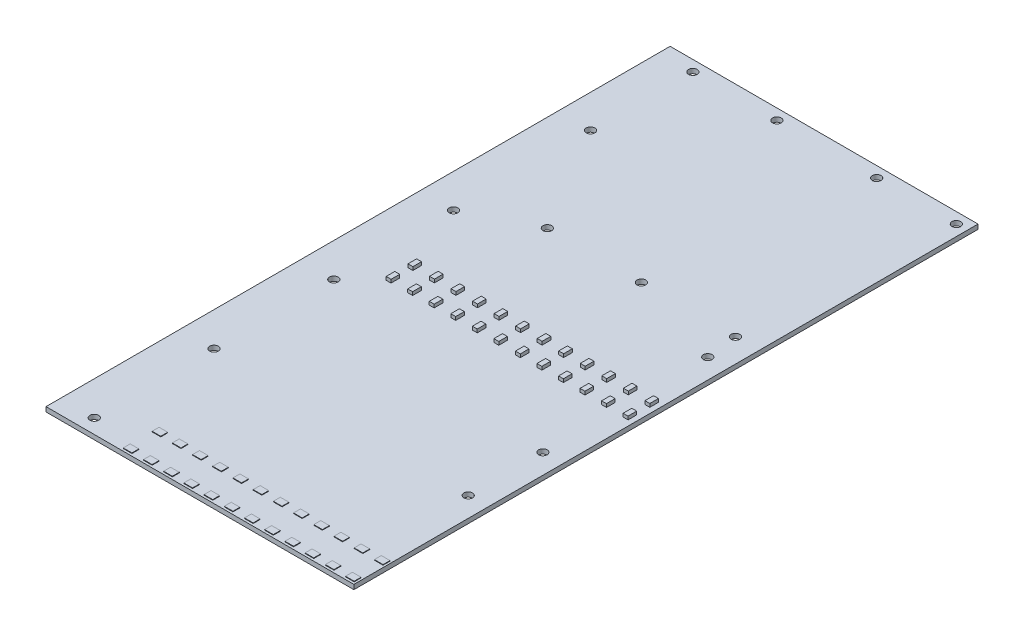
SolidWorks part; units mm, degrees
ref_plane "Front Plane" through (0, 0, 0) normal (0, 0, 1) x (1, 0, 0)
ref_plane "Top Plane" through (0, 0, 0) normal (0, 1, 0) x (1, 0, 0)
ref_plane "Right Plane" through (0, 0, 0) normal (1, 0, 0) x (0, 0, -1)
sketch "Sketch1" plane through (0, 0, 0) normal (0, 1, 0) x (1, 0, 0)
  line L1 (-53.335, 108.115) -> (53.335, 108.115)
  line L2 (-53.335, 108.115) -> (-53.335, -108.115)
  line L3 (-53.335, -108.115) -> (53.335, -108.115)
  line L4 (53.335, 108.115) -> (53.335, -108.115)
  line L5 (-53.335, 108.115) -> (53.335, -108.115) construction
  line L6 (-53.335, -108.115) -> (53.335, 108.115) construction
  point P0 (0, 0)
  dimension "D1" = 106.67
  dimension "D2" = 216.23
extrude "Boss-Extrude1" add sketch "Sketch1" along normal blind 1.6
ref_plane "Plane1" through (0, 0.8, 0) normal (0, -1, 0) x (-1, 0, 0)
sketch "Sketch4"
  dimension "D1" = 53.04
  dimension "D2" = 81.4
sketch_block_instance "motorBaseHoles-1"
sketch_block "Block1" parameters "D3"=3, "D7"=4.8524, "D1"=81.2, "D2"=7, "D4"=7, "D5"=7, "D6"=4.4351
sketch "Sketch6" plane through (0, 0, 0) normal (0, -1, 0) x (1, 0, 0)
  line L0 (12.635, 97.5334) -> (12.635, 107.6142) construction
  line L1 (-53.335, 108.115) -> (53.335, 108.115) construction
  line L2 (-25.865, 107.115) -> (-25.865, 97.1142) construction
  line L3 (-27.215, 107.115) -> (-24.515, 107.115) construction
  line L4 (-27.215, 107.115) -> (-27.215, 95.115) construction
  line L5 (-27.215, 95.115) -> (-24.515, 95.115) construction
  line L6 (-24.515, 107.115) -> (-24.515, 95.115) construction
  line L7 (-25.865, 104.915) -> (-25.865, 107.115) construction
  line L8 (-27.365, 107.315) -> (-24.365, 107.315)
  line L9 (-27.365, 107.315) -> (-27.365, 104.915)
  line L10 (-27.365, 104.915) -> (-24.365, 104.915)
  line L11 (-24.365, 107.315) -> (-24.365, 104.915)
  line L12 (-27.215, 101.115) -> (-24.515, 101.115) construction
  line L13 (-24.365, 94.915) -> (-24.365, 97.315)
  line L14 (-27.365, 97.315) -> (-24.365, 97.315)
  line L15 (-27.365, 94.915) -> (-27.365, 97.315)
  line L16 (-27.365, 94.915) -> (-24.365, 94.915)
  line L17 (-20.365, 107.315) -> (-17.365, 107.315)
  line L18 (-20.365, 107.315) -> (-20.365, 104.915)
  line L19 (-20.365, 104.915) -> (-17.365, 104.915)
  line L20 (-17.365, 107.315) -> (-17.365, 104.915)
  line L21 (-17.365, 94.915) -> (-17.365, 97.315)
  line L22 (-20.365, 97.315) -> (-17.365, 97.315)
  line L23 (-20.365, 94.915) -> (-20.365, 97.315)
  line L24 (-20.365, 94.915) -> (-17.365, 94.915)
  line L25 (-20.215, 107.115) -> (-17.515, 107.115) construction
  line L26 (-20.215, 107.115) -> (-20.215, 95.115) construction
  line L27 (-20.215, 95.115) -> (-17.515, 95.115) construction
  line L28 (-17.515, 107.115) -> (-17.515, 95.115) construction
  line L29 (-18.865, 104.915) -> (-18.865, 107.115) construction
  line L30 (-20.215, 101.115) -> (-17.515, 101.115) construction
  line L31 (-13.365, 107.315) -> (-10.365, 107.315)
  line L32 (-13.365, 107.315) -> (-13.365, 104.915)
  line L33 (-13.365, 104.915) -> (-10.365, 104.915)
  line L34 (-10.365, 107.315) -> (-10.365, 104.915)
  line L35 (-10.365, 94.915) -> (-10.365, 97.315)
  line L36 (-13.365, 97.315) -> (-10.365, 97.315)
  line L37 (-13.365, 94.915) -> (-13.365, 97.315)
  line L38 (-13.365, 94.915) -> (-10.365, 94.915)
  line L39 (-13.215, 107.115) -> (-10.515, 107.115) construction
  line L40 (-13.215, 107.115) -> (-13.215, 95.115) construction
  line L41 (-13.215, 95.115) -> (-10.515, 95.115) construction
  line L42 (-10.515, 107.115) -> (-10.515, 95.115) construction
  line L43 (-11.865, 104.915) -> (-11.865, 107.115) construction
  line L44 (-13.215, 101.115) -> (-10.515, 101.115) construction
  line L45 (-6.365, 107.315) -> (-3.365, 107.315)
  line L46 (-6.365, 107.315) -> (-6.365, 104.915)
  line L47 (-6.365, 104.915) -> (-3.365, 104.915)
  line L48 (-3.365, 107.315) -> (-3.365, 104.915)
  line L49 (-3.365, 94.915) -> (-3.365, 97.315)
  line L50 (-6.365, 97.315) -> (-3.365, 97.315)
  line L51 (-6.365, 94.915) -> (-6.365, 97.315)
  line L52 (-6.365, 94.915) -> (-3.365, 94.915)
  line L53 (-6.215, 107.115) -> (-3.515, 107.115) construction
  line L54 (-6.215, 107.115) -> (-6.215, 95.115) construction
  line L55 (-6.215, 95.115) -> (-3.515, 95.115) construction
  line L56 (-3.515, 107.115) -> (-3.515, 95.115) construction
  line L57 (-4.865, 104.915) -> (-4.865, 107.115) construction
  line L58 (-6.215, 101.115) -> (-3.515, 101.115) construction
  line L59 (0.635, 107.315) -> (3.635, 107.315)
  line L60 (0.635, 107.315) -> (0.635, 104.915)
  line L61 (0.635, 104.915) -> (3.635, 104.915)
  line L62 (3.635, 107.315) -> (3.635, 104.915)
  line L63 (3.635, 94.915) -> (3.635, 97.315)
  line L64 (0.635, 97.315) -> (3.635, 97.315)
  line L65 (0.635, 94.915) -> (0.635, 97.315)
  line L66 (0.635, 94.915) -> (3.635, 94.915)
  line L67 (0.785, 107.115) -> (3.485, 107.115) construction
  line L68 (0.785, 107.115) -> (0.785, 95.115) construction
  line L69 (0.785, 95.115) -> (3.485, 95.115) construction
  line L70 (3.485, 107.115) -> (3.485, 95.115) construction
  line L71 (2.135, 104.915) -> (2.135, 107.115) construction
  line L72 (0.785, 101.115) -> (3.485, 101.115) construction
  line L73 (7.635, 107.315) -> (10.635, 107.315)
  line L74 (7.635, 107.315) -> (7.635, 104.915)
  line L75 (7.635, 104.915) -> (10.635, 104.915)
  line L76 (10.635, 107.315) -> (10.635, 104.915)
  line L77 (10.635, 94.915) -> (10.635, 97.315)
  line L78 (7.635, 97.315) -> (10.635, 97.315)
  line L79 (7.635, 94.915) -> (7.635, 97.315)
  line L80 (7.635, 94.915) -> (10.635, 94.915)
  line L81 (7.785, 107.115) -> (10.485, 107.115) construction
  line L82 (7.785, 107.115) -> (7.785, 95.115) construction
  line L83 (7.785, 95.115) -> (10.485, 95.115) construction
  line L84 (10.485, 107.115) -> (10.485, 95.115) construction
  line L85 (9.135, 104.915) -> (9.135, 107.115) construction
  line L86 (7.785, 101.115) -> (10.485, 101.115) construction
  line L87 (14.635, 107.315) -> (17.635, 107.315)
  line L88 (14.635, 107.315) -> (14.635, 104.915)
  line L89 (14.635, 104.915) -> (17.635, 104.915)
  line L90 (17.635, 107.315) -> (17.635, 104.915)
  line L91 (17.635, 94.915) -> (17.635, 97.315)
  line L92 (14.635, 97.315) -> (17.635, 97.315)
  line L93 (14.635, 94.915) -> (14.635, 97.315)
  line L94 (14.635, 94.915) -> (17.635, 94.915)
  line L95 (14.785, 107.115) -> (17.485, 107.115) construction
  line L96 (14.785, 107.115) -> (14.785, 95.115) construction
  line L97 (14.785, 95.115) -> (17.485, 95.115) construction
  line L98 (17.485, 107.115) -> (17.485, 95.115) construction
  line L99 (16.135, 104.915) -> (16.135, 107.115) construction
  line L100 (14.785, 101.115) -> (17.485, 101.115) construction
  line L101 (21.635, 107.315) -> (24.635, 107.315)
  line L102 (21.635, 107.315) -> (21.635, 104.915)
  line L103 (21.635, 104.915) -> (24.635, 104.915)
  line L104 (24.635, 107.315) -> (24.635, 104.915)
  line L105 (24.635, 94.915) -> (24.635, 97.315)
  line L106 (21.635, 97.315) -> (24.635, 97.315)
  line L107 (21.635, 94.915) -> (21.635, 97.315)
  line L108 (21.635, 94.915) -> (24.635, 94.915)
  line L109 (21.785, 107.115) -> (24.485, 107.115) construction
  line L110 (21.785, 107.115) -> (21.785, 95.115) construction
  line L111 (21.785, 95.115) -> (24.485, 95.115) construction
  line L112 (24.485, 107.115) -> (24.485, 95.115) construction
  line L113 (23.135, 104.915) -> (23.135, 107.115) construction
  line L114 (21.785, 101.115) -> (24.485, 101.115) construction
  line L115 (28.635, 107.315) -> (31.635, 107.315)
  line L116 (28.635, 107.315) -> (28.635, 104.915)
  line L117 (28.635, 104.915) -> (31.635, 104.915)
  line L118 (31.635, 107.315) -> (31.635, 104.915)
  line L119 (31.635, 94.915) -> (31.635, 97.315)
  line L120 (28.635, 97.315) -> (31.635, 97.315)
  line L121 (28.635, 94.915) -> (28.635, 97.315)
  line L122 (28.635, 94.915) -> (31.635, 94.915)
  line L123 (28.785, 107.115) -> (31.485, 107.115) construction
  line L124 (28.785, 107.115) -> (28.785, 95.115) construction
  line L125 (28.785, 95.115) -> (31.485, 95.115) construction
  line L126 (31.485, 107.115) -> (31.485, 95.115) construction
  line L127 (30.135, 104.915) -> (30.135, 107.115) construction
  line L128 (28.785, 101.115) -> (31.485, 101.115) construction
  line L129 (35.635, 107.315) -> (38.635, 107.315)
  line L130 (35.635, 107.315) -> (35.635, 104.915)
  line L131 (35.635, 104.915) -> (38.635, 104.915)
  line L132 (38.635, 107.315) -> (38.635, 104.915)
  line L133 (38.635, 94.915) -> (38.635, 97.315)
  line L134 (35.635, 97.315) -> (38.635, 97.315)
  line L135 (35.635, 94.915) -> (35.635, 97.315)
  line L136 (35.635, 94.915) -> (38.635, 94.915)
  line L137 (35.785, 107.115) -> (38.485, 107.115) construction
  line L138 (35.785, 107.115) -> (35.785, 95.115) construction
  line L139 (35.785, 95.115) -> (38.485, 95.115) construction
  line L140 (38.485, 107.115) -> (38.485, 95.115) construction
  line L141 (37.135, 104.915) -> (37.135, 107.115) construction
  line L142 (35.785, 101.115) -> (38.485, 101.115) construction
  line L143 (42.635, 107.315) -> (45.635, 107.315)
  line L144 (42.635, 107.315) -> (42.635, 104.915)
  line L145 (42.635, 104.915) -> (45.635, 104.915)
  line L146 (45.635, 107.315) -> (45.635, 104.915)
  line L147 (45.635, 94.915) -> (45.635, 97.315)
  line L148 (42.635, 97.315) -> (45.635, 97.315)
  line L149 (42.635, 94.915) -> (42.635, 97.315)
  line L150 (42.635, 94.915) -> (45.635, 94.915)
  line L151 (42.785, 107.115) -> (45.485, 107.115) construction
  line L152 (42.785, 107.115) -> (42.785, 95.115) construction
  line L153 (42.785, 95.115) -> (45.485, 95.115) construction
  line L154 (45.485, 107.115) -> (45.485, 95.115) construction
  line L155 (44.135, 104.915) -> (44.135, 107.115) construction
  line L156 (42.785, 101.115) -> (45.485, 101.115) construction
  line L157 (49.635, 107.315) -> (52.635, 107.315)
  line L158 (49.635, 107.315) -> (49.635, 104.915)
  line L159 (49.635, 104.915) -> (52.635, 104.915)
  line L160 (52.635, 107.315) -> (52.635, 104.915)
  line L161 (52.635, 94.915) -> (52.635, 97.315)
  line L162 (49.635, 97.315) -> (52.635, 97.315)
  line L163 (49.635, 94.915) -> (49.635, 97.315)
  line L164 (49.635, 94.915) -> (52.635, 94.915)
  line L165 (49.785, 107.115) -> (52.485, 107.115) construction
  line L166 (49.785, 107.115) -> (49.785, 95.115) construction
  line L167 (49.785, 95.115) -> (52.485, 95.115) construction
  line L168 (52.485, 107.115) -> (52.485, 95.115) construction
  line L169 (51.135, 104.915) -> (51.135, 107.115) construction
  line L170 (49.785, 101.115) -> (52.485, 101.115) construction
  line L171 (51.135, 107.115) -> (51.135, 97.1142) construction
  line L172 (53.335, 0) -> (-28.065, 0) construction
  line L173 (53.335, 0) -> (-28.065, 0) construction
  line L174 (12.635, 0) -> (12.635, 97.5334) construction
  line B0 (-21.365, 120.6142) -> (-16.365, 120.6142) construction
  line B1 (-28.865, 121.1142) -> (-22.865, 121.1142) construction
  line B2 (-28.865, 121.1142) -> (-28.865, 115.1142) construction
  line B3 (-28.865, 115.1142) -> (-22.865, 115.1142) construction
  line B4 (-22.865, 121.1142) -> (-22.865, 115.1142) construction
  line B5 (-28.865, 121.1142) -> (-22.865, 115.1142) construction
  line B6 (-28.865, 115.1142) -> (-22.865, 121.1142) construction
  line B7 (-28.365, 120.6142) -> (-23.365, 120.6142) construction
  line B8 (-28.365, 120.6142) -> (-28.365, 115.6142) construction
  line B9 (-28.365, 115.6142) -> (-23.365, 115.6142) construction
  line B10 (-23.365, 120.6142) -> (-23.365, 115.6142) construction
  line B11 (-28.365, 120.6142) -> (-23.365, 115.6142) construction
  line B12 (-28.365, 115.6142) -> (-23.365, 120.6142) construction
  line B13 (-21.365, 120.6142) -> (-21.365, 115.6142) construction
  line B14 (-21.365, 115.6142) -> (-16.365, 115.6142) construction
  line B15 (-16.365, 120.6142) -> (-16.365, 115.6142) construction
  line B16 (-21.865, 121.1142) -> (-15.865, 121.1142) construction
  line B17 (-21.865, 121.1142) -> (-21.865, 115.1142) construction
  line B18 (-21.865, 115.1142) -> (-15.865, 115.1142) construction
  line B19 (-15.865, 121.1142) -> (-15.865, 115.1142) construction
  line B20 (-21.865, 121.1142) -> (-15.865, 115.1142) construction
  line B21 (-21.865, 115.1142) -> (-15.865, 121.1142) construction
  line B22 (-21.365, 120.6142) -> (-16.365, 115.6142) construction
  line B23 (-21.365, 115.6142) -> (-16.365, 120.6142) construction
  line B24 (-14.365, 120.6142) -> (-9.365, 120.6142) construction
  line B25 (-14.365, 120.6142) -> (-14.365, 115.6142) construction
  line B26 (-14.365, 115.6142) -> (-9.365, 115.6142) construction
  line B27 (-9.365, 120.6142) -> (-9.365, 115.6142) construction
  line B28 (-14.865, 121.1142) -> (-8.865, 121.1142) construction
  line B29 (-14.865, 121.1142) -> (-14.865, 115.1142) construction
  line B30 (-14.865, 115.1142) -> (-8.865, 115.1142) construction
  line B31 (-8.865, 121.1142) -> (-8.865, 115.1142) construction
  line B32 (-14.865, 121.1142) -> (-8.865, 115.1142) construction
  line B33 (-14.865, 115.1142) -> (-8.865, 121.1142) construction
  line B34 (-14.365, 120.6142) -> (-9.365, 115.6142) construction
  line B35 (-14.365, 115.6142) -> (-9.365, 120.6142) construction
  line B36 (-7.365, 120.6142) -> (-2.365, 120.6142) construction
  line B37 (-7.365, 120.6142) -> (-7.365, 115.6142) construction
  line B38 (-7.365, 115.6142) -> (-2.365, 115.6142) construction
  line B39 (-2.365, 120.6142) -> (-2.365, 115.6142) construction
  line B40 (-7.865, 121.1142) -> (-1.865, 121.1142) construction
  line B41 (-7.865, 121.1142) -> (-7.865, 115.1142) construction
  line B42 (-7.865, 115.1142) -> (-1.865, 115.1142) construction
  line B43 (-1.865, 121.1142) -> (-1.865, 115.1142) construction
  line B44 (-7.865, 121.1142) -> (-1.865, 115.1142) construction
  line B45 (-7.865, 115.1142) -> (-1.865, 121.1142) construction
  line B46 (-7.365, 120.6142) -> (-2.365, 115.6142) construction
  line B47 (-7.365, 115.6142) -> (-2.365, 120.6142) construction
  line B48 (-0.365, 120.6142) -> (4.635, 120.6142) construction
  line B49 (-0.365, 120.6142) -> (-0.365, 115.6142) construction
  line B50 (-0.365, 115.6142) -> (4.635, 115.6142) construction
  line B51 (4.635, 120.6142) -> (4.635, 115.6142) construction
  line B52 (-0.865, 121.1142) -> (5.135, 121.1142) construction
  line B53 (-0.865, 121.1142) -> (-0.865, 115.1142) construction
  line B54 (-0.865, 115.1142) -> (5.135, 115.1142) construction
  line B55 (5.135, 121.1142) -> (5.135, 115.1142) construction
  line B56 (-0.865, 121.1142) -> (5.135, 115.1142) construction
  line B57 (-0.865, 115.1142) -> (5.135, 121.1142) construction
  line B58 (-0.365, 120.6142) -> (4.635, 115.6142) construction
  line B59 (-0.365, 115.6142) -> (4.635, 120.6142) construction
  line B60 (6.635, 120.6142) -> (11.635, 120.6142) construction
  line B61 (6.635, 120.6142) -> (6.635, 115.6142) construction
  line B62 (6.635, 115.6142) -> (11.635, 115.6142) construction
  line B63 (11.635, 120.6142) -> (11.635, 115.6142) construction
  line B64 (6.135, 121.1142) -> (12.135, 121.1142) construction
  line B65 (6.135, 121.1142) -> (6.135, 115.1142) construction
  line B66 (6.135, 115.1142) -> (12.135, 115.1142) construction
  line B67 (12.135, 121.1142) -> (12.135, 115.1142) construction
  line B68 (6.135, 121.1142) -> (12.135, 115.1142) construction
  line B69 (6.135, 115.1142) -> (12.135, 121.1142) construction
  line B70 (6.635, 120.6142) -> (11.635, 115.6142) construction
  line B71 (6.635, 115.6142) -> (11.635, 120.6142) construction
  line B72 (13.635, 120.6142) -> (18.635, 120.6142) construction
  line B73 (13.635, 120.6142) -> (13.635, 115.6142) construction
  line B74 (13.635, 115.6142) -> (18.635, 115.6142) construction
  line B75 (18.635, 120.6142) -> (18.635, 115.6142) construction
  line B76 (13.135, 121.1142) -> (19.135, 121.1142) construction
  line B77 (13.135, 121.1142) -> (13.135, 115.1142) construction
  line B78 (13.135, 115.1142) -> (19.135, 115.1142) construction
  line B79 (19.135, 121.1142) -> (19.135, 115.1142) construction
  line B80 (13.135, 121.1142) -> (19.135, 115.1142) construction
  line B81 (13.135, 115.1142) -> (19.135, 121.1142) construction
  line B82 (13.635, 120.6142) -> (18.635, 115.6142) construction
  line B83 (13.635, 115.6142) -> (18.635, 120.6142) construction
  line B84 (20.635, 120.6142) -> (25.635, 120.6142) construction
  line B85 (20.635, 120.6142) -> (20.635, 115.6142) construction
  line B86 (20.635, 115.6142) -> (25.635, 115.6142) construction
  line B87 (25.635, 120.6142) -> (25.635, 115.6142) construction
  line B88 (20.135, 121.1142) -> (26.135, 121.1142) construction
  line B89 (20.135, 121.1142) -> (20.135, 115.1142) construction
  line B90 (20.135, 115.1142) -> (26.135, 115.1142) construction
  line B91 (26.135, 121.1142) -> (26.135, 115.1142) construction
  line B92 (20.135, 121.1142) -> (26.135, 115.1142) construction
  line B93 (20.135, 115.1142) -> (26.135, 121.1142) construction
  line B94 (20.635, 120.6142) -> (25.635, 115.6142) construction
  line B95 (20.635, 115.6142) -> (25.635, 120.6142) construction
  line B96 (27.635, 120.6142) -> (32.635, 120.6142) construction
  line B97 (27.635, 120.6142) -> (27.635, 115.6142) construction
  line B98 (27.635, 115.6142) -> (32.635, 115.6142) construction
  line B99 (32.635, 120.6142) -> (32.635, 115.6142) construction
  line B100 (27.135, 121.1142) -> (33.135, 121.1142) construction
  line B101 (27.135, 121.1142) -> (27.135, 115.1142) construction
  line B102 (27.135, 115.1142) -> (33.135, 115.1142) construction
  line B103 (33.135, 121.1142) -> (33.135, 115.1142) construction
  line B104 (27.135, 121.1142) -> (33.135, 115.1142) construction
  line B105 (27.135, 115.1142) -> (33.135, 121.1142) construction
  line B106 (27.635, 120.6142) -> (32.635, 115.6142) construction
  line B107 (27.635, 115.6142) -> (32.635, 120.6142) construction
  line B108 (34.635, 120.6142) -> (39.635, 120.6142) construction
  line B109 (34.635, 120.6142) -> (34.635, 115.6142) construction
  line B110 (34.635, 115.6142) -> (39.635, 115.6142) construction
  line B111 (39.635, 120.6142) -> (39.635, 115.6142) construction
  line B112 (34.135, 121.1142) -> (40.135, 121.1142) construction
  line B113 (34.135, 121.1142) -> (34.135, 115.1142) construction
  line B114 (34.135, 115.1142) -> (40.135, 115.1142) construction
  line B115 (40.135, 121.1142) -> (40.135, 115.1142) construction
  line B116 (34.135, 121.1142) -> (40.135, 115.1142) construction
  line B117 (34.135, 115.1142) -> (40.135, 121.1142) construction
  line B118 (34.635, 120.6142) -> (39.635, 115.6142) construction
  line B119 (34.635, 115.6142) -> (39.635, 120.6142) construction
  line B120 (41.635, 120.6142) -> (46.635, 120.6142) construction
  line B121 (41.635, 120.6142) -> (41.635, 115.6142) construction
  line B122 (41.635, 115.6142) -> (46.635, 115.6142) construction
  line B123 (46.635, 120.6142) -> (46.635, 115.6142) construction
  line B124 (41.135, 121.1142) -> (47.135, 121.1142) construction
  line B125 (41.135, 121.1142) -> (41.135, 115.1142) construction
  line B126 (41.135, 115.1142) -> (47.135, 115.1142) construction
  line B127 (47.135, 121.1142) -> (47.135, 115.1142) construction
  line B128 (41.135, 121.1142) -> (47.135, 115.1142) construction
  line B129 (41.135, 115.1142) -> (47.135, 121.1142) construction
  line B130 (41.635, 120.6142) -> (46.635, 115.6142) construction
  line B131 (41.635, 115.6142) -> (46.635, 120.6142) construction
  line B132 (48.635, 120.6142) -> (53.635, 120.6142) construction
  line B133 (48.635, 120.6142) -> (48.635, 115.6142) construction
  line B134 (48.635, 115.6142) -> (53.635, 115.6142) construction
  line B135 (53.635, 120.6142) -> (53.635, 115.6142) construction
  line B136 (48.135, 121.1142) -> (54.135, 121.1142) construction
  line B137 (48.135, 121.1142) -> (48.135, 115.1142) construction
  line B138 (48.135, 115.1142) -> (54.135, 115.1142) construction
  line B139 (54.135, 121.1142) -> (54.135, 115.1142) construction
  line B140 (48.135, 121.1142) -> (54.135, 115.1142) construction
  line B141 (48.135, 115.1142) -> (54.135, 121.1142) construction
  line B142 (48.635, 120.6142) -> (53.635, 115.6142) construction
  line B143 (48.635, 115.6142) -> (53.635, 120.6142) construction
  line B144 (-21.365, 113.6142) -> (-16.365, 113.6142) construction
  line B145 (-28.365, 113.6142) -> (-23.365, 113.6142) construction
  line B146 (-28.365, 113.6142) -> (-28.365, 108.6142) construction
  line B147 (-28.365, 108.6142) -> (-23.365, 108.6142) construction
  line B148 (-23.365, 113.6142) -> (-23.365, 108.6142) construction
  line B149 (-21.365, 113.6142) -> (-21.365, 108.6142) construction
  line B150 (-21.365, 108.6142) -> (-16.365, 108.6142) construction
  line B151 (-16.365, 113.6142) -> (-16.365, 108.6142) construction
  line B152 (-14.365, 113.6142) -> (-9.365, 113.6142) construction
  line B153 (-14.365, 113.6142) -> (-14.365, 108.6142) construction
  line B154 (-14.365, 108.6142) -> (-9.365, 108.6142) construction
  line B155 (-9.365, 113.6142) -> (-9.365, 108.6142) construction
  line B156 (-7.365, 113.6142) -> (-2.365, 113.6142) construction
  line B157 (-7.365, 113.6142) -> (-7.365, 108.6142) construction
  line B158 (-7.365, 108.6142) -> (-2.365, 108.6142) construction
  line B159 (-2.365, 113.6142) -> (-2.365, 108.6142) construction
  line B160 (-0.365, 113.6142) -> (4.635, 113.6142) construction
  line B161 (-0.365, 113.6142) -> (-0.365, 108.6142) construction
  line B162 (-0.365, 108.6142) -> (4.635, 108.6142) construction
  line B163 (4.635, 113.6142) -> (4.635, 108.6142) construction
  line B164 (6.635, 113.6142) -> (11.635, 113.6142) construction
  line B165 (6.635, 113.6142) -> (6.635, 108.6142) construction
  line B166 (6.635, 108.6142) -> (11.635, 108.6142) construction
  line B167 (11.635, 113.6142) -> (11.635, 108.6142) construction
  line B168 (13.635, 113.6142) -> (18.635, 113.6142) construction
  line B169 (13.635, 113.6142) -> (13.635, 108.6142) construction
  line B170 (13.635, 108.6142) -> (18.635, 108.6142) construction
  line B171 (18.635, 113.6142) -> (18.635, 108.6142) construction
  line B172 (20.635, 113.6142) -> (25.635, 113.6142) construction
  line B173 (20.635, 113.6142) -> (20.635, 108.6142) construction
  line B174 (20.635, 108.6142) -> (25.635, 108.6142) construction
  line B175 (25.635, 113.6142) -> (25.635, 108.6142) construction
  line B176 (27.635, 113.6142) -> (32.635, 113.6142) construction
  line B177 (27.635, 113.6142) -> (27.635, 108.6142) construction
  line B178 (27.635, 108.6142) -> (32.635, 108.6142) construction
  line B179 (32.635, 113.6142) -> (32.635, 108.6142) construction
  line B180 (34.635, 113.6142) -> (39.635, 113.6142) construction
  line B181 (34.635, 113.6142) -> (34.635, 108.6142) construction
  line B182 (34.635, 108.6142) -> (39.635, 108.6142) construction
  line B183 (39.635, 113.6142) -> (39.635, 108.6142) construction
  line B184 (41.635, 113.6142) -> (46.635, 113.6142) construction
  line B185 (41.635, 113.6142) -> (41.635, 108.6142) construction
  line B186 (41.635, 108.6142) -> (46.635, 108.6142) construction
  line B187 (46.635, 113.6142) -> (46.635, 108.6142) construction
  line B188 (48.635, 113.6142) -> (53.635, 113.6142) construction
  line B189 (48.635, 113.6142) -> (48.635, 108.6142) construction
  line B190 (48.635, 108.6142) -> (53.635, 108.6142) construction
  line B191 (53.635, 113.6142) -> (53.635, 108.6142) construction
  line B192 (-28.865, 114.1142) -> (-22.865, 114.1142) construction
  line B193 (-28.865, 114.1142) -> (-28.865, 108.1142) construction
  line B194 (-28.865, 108.1142) -> (-22.865, 108.1142) construction
  line B195 (-22.865, 114.1142) -> (-22.865, 108.1142) construction
  line B196 (-28.865, 114.1142) -> (-22.865, 108.1142) construction
  line B197 (-28.865, 108.1142) -> (-22.865, 114.1142) construction
  line B198 (-28.365, 113.6142) -> (-23.365, 108.6142) construction
  line B199 (-28.365, 108.6142) -> (-23.365, 113.6142) construction
  line B200 (-21.865, 114.1142) -> (-15.865, 114.1142) construction
  line B201 (-21.865, 114.1142) -> (-21.865, 108.1142) construction
  line B202 (-21.865, 108.1142) -> (-15.865, 108.1142) construction
  line B203 (-15.865, 114.1142) -> (-15.865, 108.1142) construction
  line B204 (-21.865, 114.1142) -> (-15.865, 108.1142) construction
  line B205 (-21.865, 108.1142) -> (-15.865, 114.1142) construction
  line B206 (-21.365, 113.6142) -> (-16.365, 108.6142) construction
  line B207 (-21.365, 108.6142) -> (-16.365, 113.6142) construction
  line B208 (-14.865, 114.1142) -> (-8.865, 114.1142) construction
  line B209 (-14.865, 114.1142) -> (-14.865, 108.1142) construction
  line B210 (-14.865, 108.1142) -> (-8.865, 108.1142) construction
  line B211 (-8.865, 114.1142) -> (-8.865, 108.1142) construction
  line B212 (-14.865, 114.1142) -> (-8.865, 108.1142) construction
  line B213 (-14.865, 108.1142) -> (-8.865, 114.1142) construction
  line B214 (-14.365, 113.6142) -> (-9.365, 108.6142) construction
  line B215 (-14.365, 108.6142) -> (-9.365, 113.6142) construction
  line B216 (-7.865, 114.1142) -> (-1.865, 114.1142) construction
  line B217 (-7.865, 114.1142) -> (-7.865, 108.1142) construction
  line B218 (-7.865, 108.1142) -> (-1.865, 108.1142) construction
  line B219 (-1.865, 114.1142) -> (-1.865, 108.1142) construction
  line B220 (-7.865, 114.1142) -> (-1.865, 108.1142) construction
  line B221 (-7.865, 108.1142) -> (-1.865, 114.1142) construction
  line B222 (-7.365, 113.6142) -> (-2.365, 108.6142) construction
  line B223 (-7.365, 108.6142) -> (-2.365, 113.6142) construction
  line B224 (-0.865, 114.1142) -> (5.135, 114.1142) construction
  line B225 (-0.865, 114.1142) -> (-0.865, 108.1142) construction
  line B226 (-0.865, 108.1142) -> (5.135, 108.1142) construction
  line B227 (5.135, 114.1142) -> (5.135, 108.1142) construction
  line B228 (-0.865, 114.1142) -> (5.135, 108.1142) construction
  line B229 (-0.865, 108.1142) -> (5.135, 114.1142) construction
  line B230 (-0.365, 113.6142) -> (4.635, 108.6142) construction
  line B231 (-0.365, 108.6142) -> (4.635, 113.6142) construction
  line B232 (6.135, 114.1142) -> (12.135, 114.1142) construction
  line B233 (6.135, 114.1142) -> (6.135, 108.1142) construction
  line B234 (6.135, 108.1142) -> (12.135, 108.1142) construction
  line B235 (12.135, 114.1142) -> (12.135, 108.1142) construction
  line B236 (6.135, 114.1142) -> (12.135, 108.1142) construction
  line B237 (6.135, 108.1142) -> (12.135, 114.1142) construction
  line B238 (6.635, 113.6142) -> (11.635, 108.6142) construction
  line B239 (6.635, 108.6142) -> (11.635, 113.6142) construction
  line B240 (13.135, 114.1142) -> (19.135, 114.1142) construction
  line B241 (13.135, 114.1142) -> (13.135, 108.1142) construction
  line B242 (13.135, 108.1142) -> (19.135, 108.1142) construction
  line B243 (19.135, 114.1142) -> (19.135, 108.1142) construction
  line B244 (13.135, 114.1142) -> (19.135, 108.1142) construction
  line B245 (13.135, 108.1142) -> (19.135, 114.1142) construction
  line B246 (13.635, 113.6142) -> (18.635, 108.6142) construction
  line B247 (13.635, 108.6142) -> (18.635, 113.6142) construction
  line B248 (20.135, 114.1142) -> (26.135, 114.1142) construction
  line B249 (20.135, 114.1142) -> (20.135, 108.1142) construction
  line B250 (20.135, 108.1142) -> (26.135, 108.1142) construction
  line B251 (26.135, 114.1142) -> (26.135, 108.1142) construction
  line B252 (20.135, 114.1142) -> (26.135, 108.1142) construction
  line B253 (20.135, 108.1142) -> (26.135, 114.1142) construction
  line B254 (20.635, 113.6142) -> (25.635, 108.6142) construction
  line B255 (20.635, 108.6142) -> (25.635, 113.6142) construction
  line B256 (27.135, 114.1142) -> (33.135, 114.1142) construction
  line B257 (27.135, 114.1142) -> (27.135, 108.1142) construction
  line B258 (27.135, 108.1142) -> (33.135, 108.1142) construction
  line B259 (33.135, 114.1142) -> (33.135, 108.1142) construction
  line B260 (27.135, 114.1142) -> (33.135, 108.1142) construction
  line B261 (27.135, 108.1142) -> (33.135, 114.1142) construction
  line B262 (27.635, 113.6142) -> (32.635, 108.6142) construction
  line B263 (27.635, 108.6142) -> (32.635, 113.6142) construction
  line B264 (34.135, 114.1142) -> (40.135, 114.1142) construction
  line B265 (34.135, 114.1142) -> (34.135, 108.1142) construction
  line B266 (34.135, 108.1142) -> (40.135, 108.1142) construction
  line B267 (40.135, 114.1142) -> (40.135, 108.1142) construction
  line B268 (34.135, 114.1142) -> (40.135, 108.1142) construction
  line B269 (34.135, 108.1142) -> (40.135, 114.1142) construction
  line B270 (34.635, 113.6142) -> (39.635, 108.6142) construction
  line B271 (34.635, 108.6142) -> (39.635, 113.6142) construction
  line B272 (41.135, 114.1142) -> (47.135, 114.1142) construction
  line B273 (41.135, 114.1142) -> (41.135, 108.1142) construction
  line B274 (41.135, 108.1142) -> (47.135, 108.1142) construction
  line B275 (47.135, 114.1142) -> (47.135, 108.1142) construction
  line B276 (41.135, 114.1142) -> (47.135, 108.1142) construction
  line B277 (41.135, 108.1142) -> (47.135, 114.1142) construction
  line B278 (41.635, 113.6142) -> (46.635, 108.6142) construction
  line B279 (41.635, 108.6142) -> (46.635, 113.6142) construction
  line B280 (48.135, 114.1142) -> (54.135, 114.1142) construction
  line B281 (48.135, 114.1142) -> (48.135, 108.1142) construction
  line B282 (48.135, 108.1142) -> (54.135, 108.1142) construction
  line B283 (54.135, 114.1142) -> (54.135, 108.1142) construction
  line B284 (48.135, 114.1142) -> (54.135, 108.1142) construction
  line B285 (48.135, 108.1142) -> (54.135, 114.1142) construction
  line B286 (48.635, 113.6142) -> (53.635, 108.6142) construction
  line B287 (48.635, 108.6142) -> (53.635, 113.6142) construction
  line B288 (-21.365, 106.6142) -> (-16.365, 106.6142) construction
  line B289 (-28.365, 106.6142) -> (-23.365, 106.6142) construction
  line B290 (-28.365, 106.6142) -> (-28.365, 101.6142) construction
  line B291 (-28.365, 101.6142) -> (-23.365, 101.6142) construction
  line B292 (-23.365, 106.6142) -> (-23.365, 101.6142) construction
  line B293 (-21.365, 106.6142) -> (-21.365, 101.6142) construction
  line B294 (-21.365, 101.6142) -> (-16.365, 101.6142) construction
  line B295 (-16.365, 106.6142) -> (-16.365, 101.6142) construction
  line B296 (-14.365, 106.6142) -> (-9.365, 106.6142) construction
  line B297 (-14.365, 106.6142) -> (-14.365, 101.6142) construction
  line B298 (-14.365, 101.6142) -> (-9.365, 101.6142) construction
  line B299 (-9.365, 106.6142) -> (-9.365, 101.6142) construction
  line B300 (-7.365, 106.6142) -> (-2.365, 106.6142) construction
  line B301 (-7.365, 106.6142) -> (-7.365, 101.6142) construction
  line B302 (-7.365, 101.6142) -> (-2.365, 101.6142) construction
  line B303 (-2.365, 106.6142) -> (-2.365, 101.6142) construction
  line B304 (-0.365, 106.6142) -> (4.635, 106.6142) construction
  line B305 (-0.365, 106.6142) -> (-0.365, 101.6142) construction
  line B306 (-0.365, 101.6142) -> (4.635, 101.6142) construction
  line B307 (4.635, 106.6142) -> (4.635, 101.6142) construction
  line B308 (6.635, 106.6142) -> (11.635, 106.6142) construction
  line B309 (6.635, 106.6142) -> (6.635, 101.6142) construction
  line B310 (6.635, 101.6142) -> (11.635, 101.6142) construction
  line B311 (11.635, 106.6142) -> (11.635, 101.6142) construction
  line B312 (13.635, 106.6142) -> (18.635, 106.6142) construction
  line B313 (13.635, 106.6142) -> (13.635, 101.6142) construction
  line B314 (13.635, 101.6142) -> (18.635, 101.6142) construction
  line B315 (18.635, 106.6142) -> (18.635, 101.6142) construction
  line B316 (20.635, 106.6142) -> (25.635, 106.6142) construction
  line B317 (20.635, 106.6142) -> (20.635, 101.6142) construction
  line B318 (20.635, 101.6142) -> (25.635, 101.6142) construction
  line B319 (25.635, 106.6142) -> (25.635, 101.6142) construction
  line B320 (27.635, 106.6142) -> (32.635, 106.6142) construction
  line B321 (27.635, 106.6142) -> (27.635, 101.6142) construction
  line B322 (27.635, 101.6142) -> (32.635, 101.6142) construction
  line B323 (32.635, 106.6142) -> (32.635, 101.6142) construction
  line B324 (34.635, 106.6142) -> (39.635, 106.6142) construction
  line B325 (34.635, 106.6142) -> (34.635, 101.6142) construction
  line B326 (34.635, 101.6142) -> (39.635, 101.6142) construction
  line B327 (39.635, 106.6142) -> (39.635, 101.6142) construction
  line B328 (41.635, 106.6142) -> (46.635, 106.6142) construction
  line B329 (41.635, 106.6142) -> (41.635, 101.6142) construction
  line B330 (41.635, 101.6142) -> (46.635, 101.6142) construction
  line B331 (46.635, 106.6142) -> (46.635, 101.6142) construction
  line B332 (48.635, 106.6142) -> (53.635, 106.6142) construction
  line B333 (48.635, 106.6142) -> (48.635, 101.6142) construction
  line B334 (48.635, 101.6142) -> (53.635, 101.6142) construction
  line B335 (53.635, 106.6142) -> (53.635, 101.6142) construction
  line B336 (-28.865, 107.1142) -> (-22.865, 107.1142) construction
  line B337 (-28.865, 107.1142) -> (-28.865, 101.1142) construction
  line B338 (-28.865, 101.1142) -> (-22.865, 101.1142) construction
  line B339 (-22.865, 107.1142) -> (-22.865, 101.1142) construction
  line B340 (-28.865, 107.1142) -> (-22.865, 101.1142) construction
  line B341 (-28.865, 101.1142) -> (-22.865, 107.1142) construction
  line B342 (-28.365, 106.6142) -> (-23.365, 101.6142) construction
  line B343 (-28.365, 101.6142) -> (-23.365, 106.6142) construction
  line B344 (-21.865, 107.1142) -> (-15.865, 107.1142) construction
  line B345 (-21.865, 107.1142) -> (-21.865, 101.1142) construction
  line B346 (-21.865, 101.1142) -> (-15.865, 101.1142) construction
  line B347 (-15.865, 107.1142) -> (-15.865, 101.1142) construction
  line B348 (-21.865, 107.1142) -> (-15.865, 101.1142) construction
  line B349 (-21.865, 101.1142) -> (-15.865, 107.1142) construction
  line B350 (-21.365, 106.6142) -> (-16.365, 101.6142) construction
  line B351 (-21.365, 101.6142) -> (-16.365, 106.6142) construction
  line B352 (-14.865, 107.1142) -> (-8.865, 107.1142) construction
  line B353 (-14.865, 107.1142) -> (-14.865, 101.1142) construction
  line B354 (-14.865, 101.1142) -> (-8.865, 101.1142) construction
  line B355 (-8.865, 107.1142) -> (-8.865, 101.1142) construction
  line B356 (-14.865, 107.1142) -> (-8.865, 101.1142) construction
  line B357 (-14.865, 101.1142) -> (-8.865, 107.1142) construction
  line B358 (-14.365, 106.6142) -> (-9.365, 101.6142) construction
  line B359 (-14.365, 101.6142) -> (-9.365, 106.6142) construction
  line B360 (-7.865, 107.1142) -> (-1.865, 107.1142) construction
  line B361 (-7.865, 107.1142) -> (-7.865, 101.1142) construction
  line B362 (-7.865, 101.1142) -> (-1.865, 101.1142) construction
  line B363 (-1.865, 107.1142) -> (-1.865, 101.1142) construction
  line B364 (-7.865, 107.1142) -> (-1.865, 101.1142) construction
  line B365 (-7.865, 101.1142) -> (-1.865, 107.1142) construction
  line B366 (-7.365, 106.6142) -> (-2.365, 101.6142) construction
  line B367 (-7.365, 101.6142) -> (-2.365, 106.6142) construction
  line B368 (-0.865, 107.1142) -> (5.135, 107.1142) construction
  line B369 (-0.865, 107.1142) -> (-0.865, 101.1142) construction
  line B370 (-0.865, 101.1142) -> (5.135, 101.1142) construction
  line B371 (5.135, 107.1142) -> (5.135, 101.1142) construction
  line B372 (-0.865, 107.1142) -> (5.135, 101.1142) construction
  line B373 (-0.865, 101.1142) -> (5.135, 107.1142) construction
  line B374 (-0.365, 106.6142) -> (4.635, 101.6142) construction
  line B375 (-0.365, 101.6142) -> (4.635, 106.6142) construction
  line B376 (6.135, 107.1142) -> (12.135, 107.1142) construction
  line B377 (6.135, 107.1142) -> (6.135, 101.1142) construction
  line B378 (6.135, 101.1142) -> (12.135, 101.1142) construction
  line B379 (12.135, 107.1142) -> (12.135, 101.1142) construction
  line B380 (6.135, 107.1142) -> (12.135, 101.1142) construction
  line B381 (6.135, 101.1142) -> (12.135, 107.1142) construction
  line B382 (6.635, 106.6142) -> (11.635, 101.6142) construction
  line B383 (6.635, 101.6142) -> (11.635, 106.6142) construction
  line B384 (13.135, 107.1142) -> (19.135, 107.1142) construction
  line B385 (13.135, 107.1142) -> (13.135, 101.1142) construction
  line B386 (13.135, 101.1142) -> (19.135, 101.1142) construction
  line B387 (19.135, 107.1142) -> (19.135, 101.1142) construction
  line B388 (13.135, 107.1142) -> (19.135, 101.1142) construction
  line B389 (13.135, 101.1142) -> (19.135, 107.1142) construction
  line B390 (13.635, 106.6142) -> (18.635, 101.6142) construction
  line B391 (13.635, 101.6142) -> (18.635, 106.6142) construction
  line B392 (20.135, 107.1142) -> (26.135, 107.1142) construction
  line B393 (20.135, 107.1142) -> (20.135, 101.1142) construction
  line B394 (20.135, 101.1142) -> (26.135, 101.1142) construction
  line B395 (26.135, 107.1142) -> (26.135, 101.1142) construction
  line B396 (20.135, 107.1142) -> (26.135, 101.1142) construction
  line B397 (20.135, 101.1142) -> (26.135, 107.1142) construction
  line B398 (20.635, 106.6142) -> (25.635, 101.6142) construction
  line B399 (20.635, 101.6142) -> (25.635, 106.6142) construction
  line B400 (27.135, 107.1142) -> (33.135, 107.1142) construction
  line B401 (27.135, 107.1142) -> (27.135, 101.1142) construction
  line B402 (27.135, 101.1142) -> (33.135, 101.1142) construction
  line B403 (33.135, 107.1142) -> (33.135, 101.1142) construction
  line B404 (27.135, 107.1142) -> (33.135, 101.1142) construction
  line B405 (27.135, 101.1142) -> (33.135, 107.1142) construction
  line B406 (27.635, 106.6142) -> (32.635, 101.6142) construction
  line B407 (27.635, 101.6142) -> (32.635, 106.6142) construction
  line B408 (34.135, 107.1142) -> (40.135, 107.1142) construction
  line B409 (34.135, 107.1142) -> (34.135, 101.1142) construction
  line B410 (34.135, 101.1142) -> (40.135, 101.1142) construction
  line B411 (40.135, 107.1142) -> (40.135, 101.1142) construction
  line B412 (34.135, 107.1142) -> (40.135, 101.1142) construction
  line B413 (34.135, 101.1142) -> (40.135, 107.1142) construction
  line B414 (34.635, 106.6142) -> (39.635, 101.6142) construction
  line B415 (34.635, 101.6142) -> (39.635, 106.6142) construction
  line B416 (41.135, 107.1142) -> (47.135, 107.1142) construction
  line B417 (41.135, 107.1142) -> (41.135, 101.1142) construction
  line B418 (41.135, 101.1142) -> (47.135, 101.1142) construction
  line B419 (47.135, 107.1142) -> (47.135, 101.1142) construction
  line B420 (41.135, 107.1142) -> (47.135, 101.1142) construction
  line B421 (41.135, 101.1142) -> (47.135, 107.1142) construction
  line B422 (41.635, 106.6142) -> (46.635, 101.6142) construction
  line B423 (41.635, 101.6142) -> (46.635, 106.6142) construction
  line B424 (48.135, 107.1142) -> (54.135, 107.1142) construction
  line B425 (48.135, 107.1142) -> (48.135, 101.1142) construction
  line B426 (48.135, 101.1142) -> (54.135, 101.1142) construction
  line B427 (54.135, 107.1142) -> (54.135, 101.1142) construction
  line B428 (48.135, 107.1142) -> (54.135, 101.1142) construction
  line B429 (48.135, 101.1142) -> (54.135, 107.1142) construction
  line B430 (48.635, 106.6142) -> (53.635, 101.6142) construction
  line B431 (48.635, 101.6142) -> (53.635, 106.6142) construction
  line B432 (-21.365, 99.6142) -> (-16.365, 99.6142) construction
  line B433 (-28.365, 99.6142) -> (-23.365, 99.6142) construction
  line B434 (-28.365, 99.6142) -> (-28.365, 94.6142) construction
  line B435 (-28.365, 94.6142) -> (-23.365, 94.6142) construction
  line B436 (-23.365, 99.6142) -> (-23.365, 94.6142) construction
  line B437 (-21.365, 99.6142) -> (-21.365, 94.6142) construction
  line B438 (-21.365, 94.6142) -> (-16.365, 94.6142) construction
  line B439 (-16.365, 99.6142) -> (-16.365, 94.6142) construction
  line B440 (-14.365, 99.6142) -> (-9.365, 99.6142) construction
  line B441 (-14.365, 99.6142) -> (-14.365, 94.6142) construction
  line B442 (-14.365, 94.6142) -> (-9.365, 94.6142) construction
  line B443 (-9.365, 99.6142) -> (-9.365, 94.6142) construction
  line B444 (-7.365, 99.6142) -> (-2.365, 99.6142) construction
  line B445 (-7.365, 99.6142) -> (-7.365, 94.6142) construction
  line B446 (-7.365, 94.6142) -> (-2.365, 94.6142) construction
  line B447 (-2.365, 99.6142) -> (-2.365, 94.6142) construction
  line B448 (-0.365, 99.6142) -> (4.635, 99.6142) construction
  line B449 (-0.365, 99.6142) -> (-0.365, 94.6142) construction
  line B450 (-0.365, 94.6142) -> (4.635, 94.6142) construction
  line B451 (4.635, 99.6142) -> (4.635, 94.6142) construction
  line B452 (6.635, 99.6142) -> (11.635, 99.6142) construction
  line B453 (6.635, 99.6142) -> (6.635, 94.6142) construction
  line B454 (6.635, 94.6142) -> (11.635, 94.6142) construction
  line B455 (11.635, 99.6142) -> (11.635, 94.6142) construction
  line B456 (13.635, 99.6142) -> (18.635, 99.6142) construction
  line B457 (13.635, 99.6142) -> (13.635, 94.6142) construction
  line B458 (13.635, 94.6142) -> (18.635, 94.6142) construction
  line B459 (18.635, 99.6142) -> (18.635, 94.6142) construction
  line B460 (20.635, 99.6142) -> (25.635, 99.6142) construction
  line B461 (20.635, 99.6142) -> (20.635, 94.6142) construction
  line B462 (20.635, 94.6142) -> (25.635, 94.6142) construction
  line B463 (25.635, 99.6142) -> (25.635, 94.6142) construction
  line B464 (27.635, 99.6142) -> (32.635, 99.6142) construction
  line B465 (27.635, 99.6142) -> (27.635, 94.6142) construction
  line B466 (27.635, 94.6142) -> (32.635, 94.6142) construction
  line B467 (32.635, 99.6142) -> (32.635, 94.6142) construction
  line B468 (34.635, 99.6142) -> (39.635, 99.6142) construction
  line B469 (34.635, 99.6142) -> (34.635, 94.6142) construction
  line B470 (34.635, 94.6142) -> (39.635, 94.6142) construction
  line B471 (39.635, 99.6142) -> (39.635, 94.6142) construction
  line B472 (41.635, 99.6142) -> (46.635, 99.6142) construction
  line B473 (41.635, 99.6142) -> (41.635, 94.6142) construction
  line B474 (41.635, 94.6142) -> (46.635, 94.6142) construction
  line B475 (46.635, 99.6142) -> (46.635, 94.6142) construction
  line B476 (48.635, 99.6142) -> (53.635, 99.6142) construction
  line B477 (48.635, 99.6142) -> (48.635, 94.6142) construction
  line B478 (48.635, 94.6142) -> (53.635, 94.6142) construction
  line B479 (53.635, 99.6142) -> (53.635, 94.6142) construction
  line B480 (-28.865, 100.1142) -> (-22.865, 100.1142) construction
  line B481 (-28.865, 100.1142) -> (-28.865, 94.1142) construction
  line B482 (-28.865, 94.1142) -> (-22.865, 94.1142) construction
  line B483 (-22.865, 100.1142) -> (-22.865, 94.1142) construction
  line B484 (-28.865, 100.1142) -> (-22.865, 94.1142) construction
  line B485 (-28.865, 94.1142) -> (-22.865, 100.1142) construction
  line B486 (-28.365, 99.6142) -> (-23.365, 94.6142) construction
  line B487 (-28.365, 94.6142) -> (-23.365, 99.6142) construction
  line B488 (-21.865, 100.1142) -> (-15.865, 100.1142) construction
  line B489 (-21.865, 100.1142) -> (-21.865, 94.1142) construction
  line B490 (-21.865, 94.1142) -> (-15.865, 94.1142) construction
  line B491 (-15.865, 100.1142) -> (-15.865, 94.1142) construction
  line B492 (-21.865, 100.1142) -> (-15.865, 94.1142) construction
  line B493 (-21.865, 94.1142) -> (-15.865, 100.1142) construction
  line B494 (-21.365, 99.6142) -> (-16.365, 94.6142) construction
  line B495 (-21.365, 94.6142) -> (-16.365, 99.6142) construction
  line B496 (-14.865, 100.1142) -> (-8.865, 100.1142) construction
  line B497 (-14.865, 100.1142) -> (-14.865, 94.1142) construction
  line B498 (-14.865, 94.1142) -> (-8.865, 94.1142) construction
  line B499 (-8.865, 100.1142) -> (-8.865, 94.1142) construction
  line B500 (-14.865, 100.1142) -> (-8.865, 94.1142) construction
  line B501 (-14.865, 94.1142) -> (-8.865, 100.1142) construction
  line B502 (-14.365, 99.6142) -> (-9.365, 94.6142) construction
  line B503 (-14.365, 94.6142) -> (-9.365, 99.6142) construction
  line B504 (-7.865, 100.1142) -> (-1.865, 100.1142) construction
  line B505 (-7.865, 100.1142) -> (-7.865, 94.1142) construction
  line B506 (-7.865, 94.1142) -> (-1.865, 94.1142) construction
  line B507 (-1.865, 100.1142) -> (-1.865, 94.1142) construction
  line B508 (-7.865, 100.1142) -> (-1.865, 94.1142) construction
  line B509 (-7.865, 94.1142) -> (-1.865, 100.1142) construction
  line B510 (-7.365, 99.6142) -> (-2.365, 94.6142) construction
  line B511 (-7.365, 94.6142) -> (-2.365, 99.6142) construction
  line B512 (-0.865, 100.1142) -> (5.135, 100.1142) construction
  line B513 (-0.865, 100.1142) -> (-0.865, 94.1142) construction
  line B514 (-0.865, 94.1142) -> (5.135, 94.1142) construction
  line B515 (5.135, 100.1142) -> (5.135, 94.1142) construction
  line B516 (-0.865, 100.1142) -> (5.135, 94.1142) construction
  line B517 (-0.865, 94.1142) -> (5.135, 100.1142) construction
  line B518 (-0.365, 99.6142) -> (4.635, 94.6142) construction
  line B519 (-0.365, 94.6142) -> (4.635, 99.6142) construction
  line B520 (6.135, 100.1142) -> (12.135, 100.1142) construction
  line B521 (6.135, 100.1142) -> (6.135, 94.1142) construction
  line B522 (6.135, 94.1142) -> (12.135, 94.1142) construction
  line B523 (12.135, 100.1142) -> (12.135, 94.1142) construction
  line B524 (6.135, 100.1142) -> (12.135, 94.1142) construction
  line B525 (6.135, 94.1142) -> (12.135, 100.1142) construction
  line B526 (6.635, 99.6142) -> (11.635, 94.6142) construction
  line B527 (6.635, 94.6142) -> (11.635, 99.6142) construction
  line B528 (13.135, 100.1142) -> (19.135, 100.1142) construction
  line B529 (13.135, 100.1142) -> (13.135, 94.1142) construction
  line B530 (13.135, 94.1142) -> (19.135, 94.1142) construction
  line B531 (19.135, 100.1142) -> (19.135, 94.1142) construction
  line B532 (13.135, 100.1142) -> (19.135, 94.1142) construction
  line B533 (13.135, 94.1142) -> (19.135, 100.1142) construction
  line B534 (13.635, 99.6142) -> (18.635, 94.6142) construction
  line B535 (13.635, 94.6142) -> (18.635, 99.6142) construction
  line B536 (20.135, 100.1142) -> (26.135, 100.1142) construction
  line B537 (20.135, 100.1142) -> (20.135, 94.1142) construction
  line B538 (20.135, 94.1142) -> (26.135, 94.1142) construction
  line B539 (26.135, 100.1142) -> (26.135, 94.1142) construction
  line B540 (20.135, 100.1142) -> (26.135, 94.1142) construction
  line B541 (20.135, 94.1142) -> (26.135, 100.1142) construction
  line B542 (20.635, 99.6142) -> (25.635, 94.6142) construction
  line B543 (20.635, 94.6142) -> (25.635, 99.6142) construction
  line B544 (27.135, 100.1142) -> (33.135, 100.1142) construction
  line B545 (27.135, 100.1142) -> (27.135, 94.1142) construction
  line B546 (27.135, 94.1142) -> (33.135, 94.1142) construction
  line B547 (33.135, 100.1142) -> (33.135, 94.1142) construction
  line B548 (27.135, 100.1142) -> (33.135, 94.1142) construction
  line B549 (27.135, 94.1142) -> (33.135, 100.1142) construction
  line B550 (27.635, 99.6142) -> (32.635, 94.6142) construction
  line B551 (27.635, 94.6142) -> (32.635, 99.6142) construction
  line B552 (34.135, 100.1142) -> (40.135, 100.1142) construction
  line B553 (34.135, 100.1142) -> (34.135, 94.1142) construction
  line B554 (34.135, 94.1142) -> (40.135, 94.1142) construction
  line B555 (40.135, 100.1142) -> (40.135, 94.1142) construction
  line B556 (34.135, 100.1142) -> (40.135, 94.1142) construction
  line B557 (34.135, 94.1142) -> (40.135, 100.1142) construction
  line B558 (34.635, 99.6142) -> (39.635, 94.6142) construction
  line B559 (34.635, 94.6142) -> (39.635, 99.6142) construction
  line B560 (41.135, 100.1142) -> (47.135, 100.1142) construction
  line B561 (41.135, 100.1142) -> (41.135, 94.1142) construction
  line B562 (41.135, 94.1142) -> (47.135, 94.1142) construction
  line B563 (47.135, 100.1142) -> (47.135, 94.1142) construction
  line B564 (41.135, 100.1142) -> (47.135, 94.1142) construction
  line B565 (41.135, 94.1142) -> (47.135, 100.1142) construction
  line B566 (41.635, 99.6142) -> (46.635, 94.6142) construction
  line B567 (41.635, 94.6142) -> (46.635, 99.6142) construction
  line B568 (48.135, 100.1142) -> (54.135, 100.1142) construction
  line B569 (48.135, 100.1142) -> (48.135, 94.1142) construction
  line B570 (48.135, 94.1142) -> (54.135, 94.1142) construction
  line B571 (54.135, 100.1142) -> (54.135, 94.1142) construction
  line B572 (48.135, 100.1142) -> (54.135, 94.1142) construction
  line B573 (48.135, 94.1142) -> (54.135, 100.1142) construction
  line B574 (48.635, 99.6142) -> (53.635, 94.6142) construction
  line B575 (48.635, 94.6142) -> (53.635, 99.6142) construction
  line B576 (-28.865, 121.1142) -> (54.135, 121.1142) construction
  line B577 (-28.865, 121.1142) -> (-28.865, 94.1142) construction
  line B578 (12.635, 121.1142) -> (12.635, 107.6142) construction
  line B579 (12.635, 107.6142) -> (-28.865, 107.6142) construction
  circle B580 centre (-25.865, 118.1142) radius 3 construction
  circle B581 centre (-18.865, 118.1142) radius 3 construction
  circle B582 centre (-11.865, 118.1142) radius 3 construction
  circle B583 centre (-4.865, 118.1142) radius 3 construction
  circle B584 centre (2.135, 118.1142) radius 3 construction
  circle B585 centre (9.135, 118.1142) radius 3 construction
  circle B586 centre (16.135, 118.1142) radius 3 construction
  circle B587 centre (23.135, 118.1142) radius 3 construction
  circle B588 centre (30.135, 118.1142) radius 3 construction
  circle B589 centre (37.135, 118.1142) radius 3 construction
  circle B590 centre (44.135, 118.1142) radius 3 construction
  circle B591 centre (51.135, 118.1142) radius 3 construction
  circle B592 centre (-25.865, 111.1142) radius 3 construction
  circle B593 centre (-18.865, 111.1142) radius 3 construction
  circle B594 centre (-11.865, 111.1142) radius 3 construction
  circle B595 centre (-4.865, 111.1142) radius 3 construction
  circle B596 centre (2.135, 111.1142) radius 3 construction
  circle B597 centre (9.135, 111.1142) radius 3 construction
  circle B598 centre (16.135, 111.1142) radius 3 construction
  circle B599 centre (23.135, 111.1142) radius 3 construction
  circle B600 centre (30.135, 111.1142) radius 3 construction
  circle B601 centre (37.135, 111.1142) radius 3 construction
  circle B602 centre (44.135, 111.1142) radius 3 construction
  circle B603 centre (51.135, 111.1142) radius 3 construction
  circle B604 centre (-25.865, 104.1142) radius 3 construction
  circle B605 centre (-18.865, 104.1142) radius 3 construction
  circle B606 centre (-11.865, 104.1142) radius 3 construction
  circle B607 centre (-4.865, 104.1142) radius 3 construction
  circle B608 centre (2.135, 104.1142) radius 3 construction
  circle B609 centre (9.135, 104.1142) radius 3 construction
  circle B610 centre (16.135, 104.1142) radius 3 construction
  circle B611 centre (23.135, 104.1142) radius 3 construction
  circle B612 centre (30.135, 104.1142) radius 3 construction
  circle B613 centre (37.135, 104.1142) radius 3 construction
  circle B614 centre (44.135, 104.1142) radius 3 construction
  circle B615 centre (51.135, 104.1142) radius 3 construction
  circle B616 centre (-25.865, 97.1142) radius 3 construction
  circle B617 centre (-18.865, 97.1142) radius 3 construction
  circle B618 centre (-11.865, 97.1142) radius 3 construction
  circle B619 centre (-4.865, 97.1142) radius 3 construction
  circle B620 centre (2.135, 97.1142) radius 3 construction
  circle B621 centre (9.135, 97.1142) radius 3 construction
  circle B622 centre (16.135, 97.1142) radius 3 construction
  circle B623 centre (23.135, 97.1142) radius 3 construction
  circle B624 centre (30.135, 97.1142) radius 3 construction
  circle B625 centre (37.135, 97.1142) radius 3 construction
  circle B626 centre (44.135, 97.1142) radius 3 construction
  circle B627 centre (51.135, 97.1142) radius 3 construction
  dimension "D1" = 12
  dimension "D2" = 2.7
  dimension "D3" = 1
  dimension "D4" = 3
  dimension "D5" = 7.6
  dimension "D6" = 12.4
  dimension "D7" = 12
sketch_block_instance "Block-topPinsTemplate-2"
sketch_block "Block-topPinsTemplate" parameters "D1"=6, "D2"=5, "D3"=1, "D4"=1
extrude "Boss-Extrude3" add sketch "Sketch6" along normal blind 0.2 contours L23 L24 L21 L22 | L34 L31 L32 L33 | L37 L38 L35 L36 | L48 L45 L46 L47 | L20 L17 L18 L19 | L11 L8 L9 L10 | L15 L16 L13 L14 | L62 L59 L60 L61 | L65 L66 L63 L64 | L51 L52 L49 L50 | L79 L80 L77 L78 | L76 L73 L74 L75 | L90 L87 L88 L89 | L93 L94 L91 L92 | L104 L101 L102 L103 | L107 L108 L105 L106 | L121 L122 L119 L120 | L118 L115 L116 L117 | L132 L129 L130 L131 | L135 L136 L133 L134 | L149 L150 L147 L148 | L146 L143 L144 L145 | L160 L157 L158 L159 | L163 L164 L161 L162 | L11 L10 L9 L8 | L18 L19 L20 L17 | L13 L14 L15 L16 region at (-25.865, 0, 106.115) region at (-25.865, 0, 96.115) region at (-18.865, 0, 106.115) region at (-18.865, 0, 96.115) region at (-11.865, 0, 106.115) region at (-11.865, 0, 96.115) region at (-4.865, 0, 106.115) region at (-4.865, 0, 96.115) region at (2.135, 0, 106.115) region at (2.135, 0, 96.115) region at (9.135, 0, 106.115) region at (9.135, 0, 96.115) region at (16.135, 0, 106.115) region at (16.135, 0, 96.115) region at (23.135, 0, 106.115) region at (23.135, 0, 96.115) region at (30.135, 0, 106.115) region at (30.135, 0, 96.115) region at (37.135, 0, 106.115) region at (37.135, 0, 96.115) region at (44.135, 0, 106.115) region at (44.135, 0, 96.115) region at (51.135, 0, 106.115) region at (51.135, 0, 96.115)
mirror "Mirror2" about plane through (0, 0.8, 0) normal (0, -1, 0) of "Boss-Extrude3"
sketch "Sketch13" plane through (0, 1.6, 0) normal (0, 1, 0) x (1, 0, 0)
  line L0 (53.335, -108.115) -> (53.335, 108.115) construction
  line L1 (53.335, 108.115) -> (-53.335, 108.115) construction
  line B0 (44.0114, -0.725) -> (42.3114, -0.725)
  line B1 (51.475, -0.725) -> (49.775, -0.725)
  line B2 (51.475, -0.725) -> (51.475, -3.725)
  line B3 (51.475, -3.725) -> (49.775, -3.725)
  line B4 (49.775, -0.725) -> (49.775, -3.725)
  line B5 (44.0114, -0.725) -> (44.0114, -3.725)
  line B6 (44.0114, -3.725) -> (42.3114, -3.725)
  line B7 (42.3114, -0.725) -> (42.3114, -3.725)
  line B8 (36.5477, -0.725) -> (34.8477, -0.725)
  line B9 (36.5477, -0.725) -> (36.5477, -3.725)
  line B10 (36.5477, -3.725) -> (34.8477, -3.725)
  line B11 (34.8477, -0.725) -> (34.8477, -3.725)
  line B12 (29.0841, -0.725) -> (27.3841, -0.725)
  line B13 (29.0841, -0.725) -> (29.0841, -3.725)
  line B14 (29.0841, -3.725) -> (27.3841, -3.725)
  line B15 (27.3841, -0.725) -> (27.3841, -3.725)
  line B16 (21.6205, -0.725) -> (19.9205, -0.725)
  line B17 (21.6205, -0.725) -> (21.6205, -3.725)
  line B18 (21.6205, -3.725) -> (19.9205, -3.725)
  line B19 (19.9205, -0.725) -> (19.9205, -3.725)
  line B20 (14.1568, -0.725) -> (12.4568, -0.725)
  line B21 (14.1568, -0.725) -> (14.1568, -3.725)
  line B22 (14.1568, -3.725) -> (12.4568, -3.725)
  line B23 (12.4568, -0.725) -> (12.4568, -3.725)
  line B24 (6.6932, -0.725) -> (4.9932, -0.725)
  line B25 (6.6932, -0.725) -> (6.6932, -3.725)
  line B26 (6.6932, -3.725) -> (4.9932, -3.725)
  line B27 (4.9932, -0.725) -> (4.9932, -3.725)
  line B28 (-0.7705, -0.725) -> (-2.4705, -0.725)
  line B29 (-0.7705, -0.725) -> (-0.7705, -3.725)
  line B30 (-0.7705, -3.725) -> (-2.4705, -3.725)
  line B31 (-2.4705, -0.725) -> (-2.4705, -3.725)
  line B32 (-8.2341, -0.725) -> (-9.9341, -0.725)
  line B33 (-8.2341, -0.725) -> (-8.2341, -3.725)
  line B34 (-8.2341, -3.725) -> (-9.9341, -3.725)
  line B35 (-9.9341, -0.725) -> (-9.9341, -3.725)
  line B36 (-15.6977, -0.725) -> (-17.3977, -0.725)
  line B37 (-15.6977, -0.725) -> (-15.6977, -3.725)
  line B38 (-15.6977, -3.725) -> (-17.3977, -3.725)
  line B39 (-17.3977, -0.725) -> (-17.3977, -3.725)
  line B40 (-23.1614, -0.725) -> (-24.8614, -0.725)
  line B41 (-23.1614, -0.725) -> (-23.1614, -3.725)
  line B42 (-23.1614, -3.725) -> (-24.8614, -3.725)
  line B43 (-24.8614, -0.725) -> (-24.8614, -3.725)
  line B44 (-30.625, -0.725) -> (-32.325, -0.725)
  line B45 (-30.625, -0.725) -> (-30.625, -3.725)
  line B46 (-30.625, -3.725) -> (-32.325, -3.725)
  line B47 (-32.325, -0.725) -> (-32.325, -3.725)
  line B48 (-32.325, -6) -> (51.475, -6) construction
  line B49 (-32.325, -11.275) -> (-32.325, -8.275)
  line B50 (-30.625, -8.275) -> (-32.325, -8.275)
  line B51 (-30.625, -11.275) -> (-30.625, -8.275)
  line B52 (-30.625, -11.275) -> (-32.325, -11.275)
  line B53 (-24.8614, -11.275) -> (-24.8614, -8.275)
  line B54 (-23.1614, -8.275) -> (-24.8614, -8.275)
  line B55 (-23.1614, -11.275) -> (-23.1614, -8.275)
  line B56 (-23.1614, -11.275) -> (-24.8614, -11.275)
  line B57 (-17.3977, -11.275) -> (-17.3977, -8.275)
  line B58 (-15.6977, -8.275) -> (-17.3977, -8.275)
  line B59 (-15.6977, -11.275) -> (-15.6977, -8.275)
  line B60 (-15.6977, -11.275) -> (-17.3977, -11.275)
  line B61 (-9.9341, -11.275) -> (-9.9341, -8.275)
  line B62 (-8.2341, -8.275) -> (-9.9341, -8.275)
  line B63 (-8.2341, -11.275) -> (-8.2341, -8.275)
  line B64 (-8.2341, -11.275) -> (-9.9341, -11.275)
  line B65 (-2.4705, -11.275) -> (-2.4705, -8.275)
  line B66 (-0.7705, -8.275) -> (-2.4705, -8.275)
  line B67 (-0.7705, -11.275) -> (-0.7705, -8.275)
  line B68 (-0.7705, -11.275) -> (-2.4705, -11.275)
  line B69 (4.9932, -11.275) -> (4.9932, -8.275)
  line B70 (6.6932, -8.275) -> (4.9932, -8.275)
  line B71 (6.6932, -11.275) -> (6.6932, -8.275)
  line B72 (6.6932, -11.275) -> (4.9932, -11.275)
  line B73 (12.4568, -11.275) -> (12.4568, -8.275)
  line B74 (14.1568, -8.275) -> (12.4568, -8.275)
  line B75 (14.1568, -11.275) -> (14.1568, -8.275)
  line B76 (14.1568, -11.275) -> (12.4568, -11.275)
  line B77 (19.9205, -11.275) -> (19.9205, -8.275)
  line B78 (21.6205, -8.275) -> (19.9205, -8.275)
  line B79 (21.6205, -11.275) -> (21.6205, -8.275)
  line B80 (21.6205, -11.275) -> (19.9205, -11.275)
  line B81 (27.3841, -11.275) -> (27.3841, -8.275)
  line B82 (29.0841, -8.275) -> (27.3841, -8.275)
  line B83 (29.0841, -11.275) -> (29.0841, -8.275)
  line B84 (29.0841, -11.275) -> (27.3841, -11.275)
  line B85 (34.8477, -11.275) -> (34.8477, -8.275)
  line B86 (36.5477, -8.275) -> (34.8477, -8.275)
  line B87 (36.5477, -11.275) -> (36.5477, -8.275)
  line B88 (36.5477, -11.275) -> (34.8477, -11.275)
  line B89 (42.3114, -11.275) -> (42.3114, -8.275)
  line B90 (44.0114, -8.275) -> (42.3114, -8.275)
  line B91 (44.0114, -11.275) -> (44.0114, -8.275)
  line B92 (49.775, -11.275) -> (49.775, -8.275)
  line B93 (51.475, -8.275) -> (49.775, -8.275)
  line B94 (51.475, -11.275) -> (51.475, -8.275)
  line B95 (51.475, -11.275) -> (49.775, -11.275)
  line B96 (44.0114, -11.275) -> (42.3114, -11.275)
  line B97 (50.625, 4.275) -> (50.625, -0.725) construction
  line B98 (-31.475, 4.275) -> (-31.475, -0.725) construction
  line B99 (50.625, -14.275) -> (50.625, -11.275) construction
  line B100 (53.05, -24.275) -> (48.2, -24.275) construction
  line B101 (53.05, -24.275) -> (53.05, -14.275) construction
  line B102 (53.05, -14.275) -> (48.2, -14.275) construction
  line B103 (48.2, -24.275) -> (48.2, -14.275) construction
  line B104 (45.5864, -24.275) -> (40.7364, -24.275) construction
  line B105 (45.5864, -24.275) -> (45.5864, -14.275) construction
  line B106 (45.5864, -14.275) -> (40.7364, -14.275) construction
  line B107 (40.7364, -24.275) -> (40.7364, -14.275) construction
  line B108 (38.1227, -24.275) -> (33.2727, -24.275) construction
  line B109 (38.1227, -24.275) -> (38.1227, -14.275) construction
  line B110 (38.1227, -14.275) -> (33.2727, -14.275) construction
  line B111 (33.2727, -24.275) -> (33.2727, -14.275) construction
  line B112 (30.6591, -24.275) -> (25.8091, -24.275) construction
  line B113 (30.6591, -24.275) -> (30.6591, -14.275) construction
  line B114 (30.6591, -14.275) -> (25.8091, -14.275) construction
  line B115 (25.8091, -24.275) -> (25.8091, -14.275) construction
  line B116 (23.1955, -24.275) -> (18.3455, -24.275) construction
  line B117 (23.1955, -24.275) -> (23.1955, -14.275) construction
  line B118 (23.1955, -14.275) -> (18.3455, -14.275) construction
  line B119 (18.3455, -24.275) -> (18.3455, -14.275) construction
  line B120 (15.7318, -24.275) -> (10.8818, -24.275) construction
  line B121 (15.7318, -24.275) -> (15.7318, -14.275) construction
  line B122 (15.7318, -14.275) -> (10.8818, -14.275) construction
  line B123 (10.8818, -24.275) -> (10.8818, -14.275) construction
  line B124 (8.2682, -24.275) -> (3.4182, -24.275) construction
  line B125 (8.2682, -24.275) -> (8.2682, -14.275) construction
  line B126 (8.2682, -14.275) -> (3.4182, -14.275) construction
  line B127 (3.4182, -24.275) -> (3.4182, -14.275) construction
  line B128 (0.8045, -24.275) -> (-4.0455, -24.275) construction
  line B129 (0.8045, -24.275) -> (0.8045, -14.275) construction
  line B130 (0.8045, -14.275) -> (-4.0455, -14.275) construction
  line B131 (-4.0455, -24.275) -> (-4.0455, -14.275) construction
  line B132 (-6.6591, -24.275) -> (-11.5091, -24.275) construction
  line B133 (-6.6591, -24.275) -> (-6.6591, -14.275) construction
  line B134 (-6.6591, -14.275) -> (-11.5091, -14.275) construction
  line B135 (-11.5091, -24.275) -> (-11.5091, -14.275) construction
  line B136 (-14.1227, -24.275) -> (-18.9727, -24.275) construction
  line B137 (-14.1227, -24.275) -> (-14.1227, -14.275) construction
  line B138 (-14.1227, -14.275) -> (-18.9727, -14.275) construction
  line B139 (-18.9727, -24.275) -> (-18.9727, -14.275) construction
  line B140 (-21.5864, -24.275) -> (-26.4364, -24.275) construction
  line B141 (-21.5864, -24.275) -> (-21.5864, -14.275) construction
  line B142 (-21.5864, -14.275) -> (-26.4364, -14.275) construction
  line B143 (-26.4364, -24.275) -> (-26.4364, -14.275) construction
  line B144 (-29.05, -24.275) -> (-33.9, -24.275) construction
  line B145 (-29.05, -24.275) -> (-29.05, -14.275) construction
  line B146 (-29.05, -14.275) -> (-33.9, -14.275) construction
  line B147 (-33.9, -24.275) -> (-33.9, -14.275) construction
  line B148 (-31.475, -14.275) -> (-31.475, -11.275) construction
  line B149 (12.555, 32.275) -> (-20.035, 32.275) construction
  line B150 (12.555, 32.275) -> (45.145, 32.275) construction
  line B151 (-20.035, 32.275) -> (-31.475, 4.275) construction
  line B152 (-20.035, 32.275) -> (-31.475, 32.275) construction
  line B153 (-31.475, 32.275) -> (-31.475, 4.275) construction
  circle B154 centre (50.625, 4.275) radius 3 construction
  circle B155 centre (43.1614, 4.275) radius 3 construction
  circle B156 centre (35.6977, 4.275) radius 3 construction
  circle B157 centre (28.2341, 4.275) radius 3 construction
  circle B158 centre (20.7705, 4.275) radius 3 construction
  circle B159 centre (13.3068, 4.275) radius 3 construction
  circle B160 centre (5.8432, 4.275) radius 3 construction
  circle B161 centre (-1.6205, 4.275) radius 3 construction
  circle B162 centre (-9.0841, 4.275) radius 3 construction
  circle B163 centre (-16.5477, 4.275) radius 3 construction
  circle B164 centre (-24.0114, 4.275) radius 3 construction
  circle B165 centre (-31.475, 4.275) radius 3 construction
  circle B166 centre (45.145, 32.275) radius 1.5 construction
  circle B167 centre (12.555, 32.275) radius 1.5 construction
  circle B168 centre (-20.035, 32.275) radius 1.5 construction
  dimension "D1" = 1.86
  dimension "D2" = 108.84
sketch_block_instance "Block-NewPCBDiagram-1"
sketch_block "Block-NewPCBDiagram" parameters "D5"=6, "D10"=3, "D1"=1.7, "D2"=3, "D3"=83.8, "D4"=10.55, "D6"=5, "D7"=4.85, "D8"=10, "D9"=3, "D11"=6.33, "D12"=33, "D13"=32.59
extrude "Boss-Extrude4" add sketch "Sketch13" along normal blind 1.15
mirror "Mirror3" about plane through (0, 0.8, 0) normal (0, -1, 0) of "Boss-Extrude4"
sketch "Sketch14" plane through (0, 1.6, 0) normal (0, 1, 0) x (1, 0, 0)
  circle A0 centre (45.145, 32.275) radius 1.5 construction
  circle A1 centre (12.555, 32.275) radius 1.5 construction
  circle A2 centre (-20.035, 32.275) radius 1.5 construction
  circle A3 centre (45.145, 32.275) radius 1.5
  circle A4 centre (12.555, 32.275) radius 1.5
  circle A5 centre (-20.035, 32.275) radius 1.5
extrude "Cut-Extrude1" cut sketch "Sketch14" against normal through all
sketch "Sketch15" plane through (0, 0, 0) normal (0, -1, 0) x (1, 0, 0)
  circle A0 centre (49.588, -104.365) radius 1.5
  circle A1 centre (12.555, -32.275) radius 1.5 construction
  circle A2 centre (21.978, -104.365) radius 1.5
  circle A3 centre (-12.591, -104.365) radius 1.5
  circle A4 centre (-41.701, -104.365) radius 1.5
  circle A5 centre (-41.879, -69.08) radius 1.5
  circle A7 centre (-20.035, -32.275) radius 1.5 construction
  circle A8 centre (-41.625, -21.373) radius 1.5
  circle A9 centre (-41.625, 20.12) radius 1.5
  circle A10 centre (-41.625, 61.613) radius 1.5
  circle A11 centre (-41.625, 103.106) radius 1.5
  circle A12 centre (46.44, -21.373) radius 1.5
  circle A13 centre (45.145, -32.275) radius 1.5 construction
  circle A14 centre (46.44, 35.747) radius 1.5
  circle A15 centre (46.44, 61.614) radius 1.5
  dimension "D3" = 3
  dimension "D5" = 34.569
  dimension "D6" = 29.11
  dimension "D7" = 3
  dimension "D8" = 3
  dimension "D9" = 3
  dimension "D10" = 36.805
  dimension "D12" = 3
  dimension "D13" = 21.59
  dimension "D14" = 10.902
  dimension "D15" = 3
  dimension "D18" = 3
  dimension "D19" = 3
  dimension "D20" = 41.493
  dimension "D21" = 3
  dimension "D24" = 3
  dimension "D26" = 3
  dimension "D28" = 3
  dimension "D1" = 37.033
  dimension "D2" = 72.09
  dimension "D4" = 27.61
  dimension "D11" = 21.844
  dimension "D16" = 41.493
  dimension "D17" = 41.493
  dimension "D22" = 1.295
  dimension "D23" = 10.902
  dimension "D25" = 57.12
  dimension "D27" = 25.867
extrude "Cut-Extrude2" cut sketch "Sketch15" against normal through all
equation "\"pcbThickness\"= 1.6"
equation "\"sideWallThickness\"= 1.5"
equation "\"bottomWallThickness\"= 6.0"
equation "\"topWallThickness\"= 2.0"
equation "\"D1@Boss-Extrude1\" = \"pcbThickness\""
equation "\"totalHeight\"= 220.50 + \"wallTolerance\""
equation "\"totalWidth\"= 12 * \"motorDiameter\" + 11 * \"motor2motorHorizontal\" + 2 * \"wallTolerance\""
equation "\"totalDepth\"= 4 * \"motorDiameter\" + 2 * \"pcbThickness\" + 1 * \"motor2motorHorizontal\" + 4 * 0.10 + 2 * \"wallTolerance\""
equation "\"D1@Sketch1\"=\"pcbWidth\""
equation "\"D2@Sketch1\"=\"pcbLength\""
equation "\"pinHeight\"= 115"
equation "\"electricalComponents\"=53.04"
equation "\"supportThickness\"=1.5"
equation "\"pinWidth\"= 4.85"
equation "\"motorDiameter\"=6.0"
equation "\"res\"= 2.0"
equation "\"pcbWidth\"= 106.67"
equation "\"pcbLength\"= 216.23"
equation "\"supportDistance\"= 10.0"
equation "\"wallTolerance\" = 0.2"
equation "\"motorSmallDiameter\"= 3.5"
equation "\"motorSmallLength\"= 0.4"
equation "\"motorShaftDiameter\"= 2.0"
equation "\"motorShaftLength\"= 2.7"
equation "\"motorShaftFlatDist\"= 1.5"
equation "\"motorWireDiameter\"= 0.5"
equation "\"D1\"= \"pcbWidth\""
equation "\"motorWireDistance\"= 3.20"
equation "\"encoderLength\"= 3.2"
equation "\"encoderWidth\"= 1.7"
equation "\"encoderDepth\"=1.1"
equation "\"encoderTolerance\"=0.15"
equation "\"encoderDistance\"=1.0"
equation "\"pcbToWall\"= \"motorDiameter\" + \"wallTolerance\""
equation "\"pcbToPcb\"= 2 * \"motorDiameter\" + \"wallTolerance\" + 1.0"
equation "\"bracketBlockWidth\"= 13.20"
equation "\"bracketBlockHeight\"= 10.0"
equation "\"D2@Sketch4\"=\"totalWidth\"-2.0"
equation "\"pcbExtension\"= 26.0"
equation "\"acrylicSideWallThickness\" = 2.0"
equation "\"smallBlockLength\"= 14"
equation "\"bottomBlockLength\"= 24"
equation "\"topBlockLength\"= 18"
equation "\"encoderToSwitchDistance\"= 7.35"
equation "\"encoderTicksSpacing\"= 0.65"
equation "\"motor2motorHorizontal\"= 1.0"
equation "\"motor2motorVertical\"= 1.80"
equation "\"length\"= 152.0"
